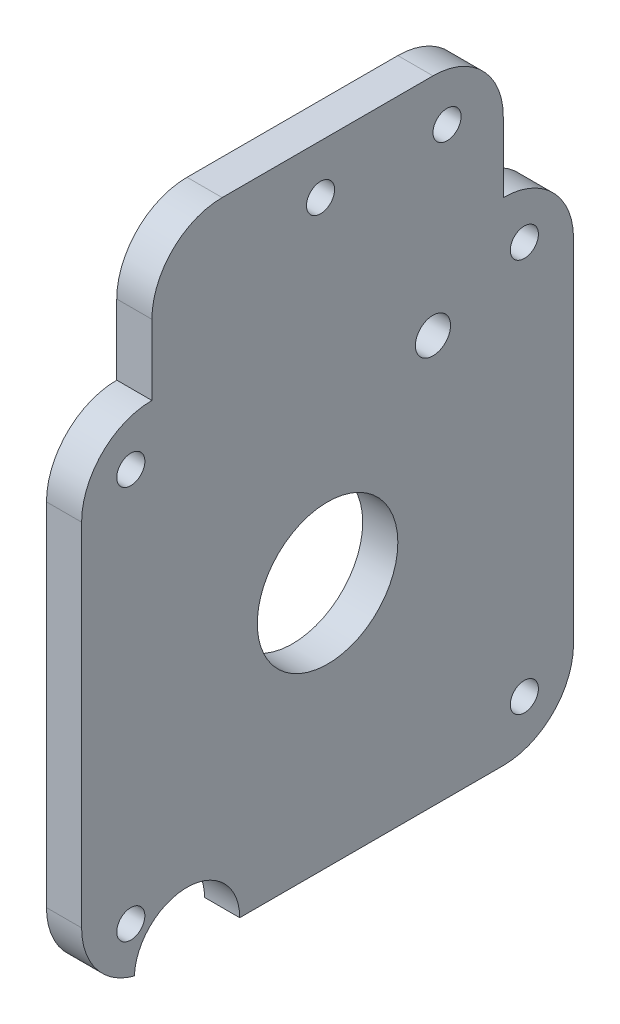
SolidWorks part; units mm, degrees
ref_plane "Alzado" through (0, 0, 0) normal (0, 0, 1) x (1, 0, 0)
ref_plane "Planta" through (0, 0, 0) normal (0, 1, 0) x (1, 0, 0)
ref_plane "Vista lateral" through (0, 0, 0) normal (1, 0, 0) x (0, 0, -1)
sketch "Croquis1" plane through (0, 0, 0) normal (1, 0, 0) x (0, 0, -1)
  line L0 (35, 70) -> (35, 35) construction
  line L1 (10, 0) -> (60, 0)
  line L2 (0, 10) -> (0, 60)
  line L3 (60, 70) -> (10, 70) construction
  line L4 (70, 10) -> (70, 60)
  line L5 (0, 35) -> (35, 35) construction
  line L8 (60, 70) -> (60, 80)
  line L9 (50, 90) -> (20, 90)
  line L10 (10, 70) -> (10, 80)
  arc A0 (10, 0) -> (0, 10) centre (10, 10) cw
  arc A1 (60, 0) -> (70, 10) centre (60, 10) ccw
  arc A2 (60, 70) -> (70, 60) centre (60, 60) cw
  arc A3 (0, 60) -> (10, 70) centre (10, 60) cw
  circle A4 centre (7, 63) radius 2
  circle A5 centre (63, 63) radius 2
  circle A6 centre (63, 7) radius 2
  circle A7 centre (7, 7) radius 2
  circle A8 centre (35, 35) radius 10
  arc A9 (20, 90) -> (10, 80) centre (20, 80) ccw
  arc A10 (60, 80) -> (50, 90) centre (50, 80) ccw
  point P7 (0, 0)
  point P12 (70, 70)
  point P15 (0, 70)
  point P34 (60, 90)
  dimension "D3" = 10
  dimension "D4" = 4
  dimension "D7" = 20
  dimension "D9" = 10
  dimension "D1" = 70
  dimension "D2" = 70
  dimension "D5" = 35
  dimension "D6" = 7
  dimension "D8" = 20
  dimension "D10" = 35
extrude "Saliente-Extruir1" add sketch "Croquis1" along normal blind 5
sketch "Croquis2" plane through (5, 0, 0) normal (1, 0, 0) x (0, 0, -1)
  line L0 (60, 70) -> (10, 70) construction
  line L1 (52, 83) -> (34, 83) construction
  line L2 (10, 0) -> (60, 0) construction
  line L3 (0, 60) -> (0, 10) construction
  line L4 (35, 35) -> (35, 70) construction
  line L5 (60, 70) -> (60, 80) construction
  circle A0 centre (15, 0) radius 7.5
  circle A1 centre (50, 58) radius 2.5
  arc A2 (10, 70) -> (0, 60) centre (10, 60) ccw construction
  circle A3 centre (52, 83) radius 2
  circle A4 centre (34, 83) radius 2
  dimension "D1" = 15
  dimension "D3" = 5
  dimension "D5" = 23
  dimension "D6" = 4
  dimension "D7" = 4
  dimension "D2" = 15
  dimension "D4" = 15
  dimension "D8" = 18
  dimension "D9" = 8
  dimension "D10" = 13
extrude "Cortar-Extruir1" cut sketch "Croquis2" against normal blind 10
sketch "Croquis3" plane through (0, 0, 0) normal (-1, 0, 0) x (0, 0, 1)
  line L6 (0, 10) -> (0, 60)
  line L7 (-10, 70) -> (-10, 80)
  line L8 (-20, 90) -> (-50, 90)
  line L9 (-60, 80) -> (-60, 70)
  line L10 (-70, 60) -> (-70, 10)
  line L11 (-60, 0) -> (-22.5, 0)
  line L12 (0, 10) -> (0, 60)
  line L13 (-10, 70) -> (-10, 80)
  line L14 (-20, 90) -> (-50, 90)
  line L15 (-60, 80) -> (-60, 70)
  line L16 (-70, 60) -> (-70, 10)
  line L17 (-60, 0) -> (-22.5, 0)
  circle A0 centre (-34, 83) radius 2 construction
  circle A1 centre (-7, 63) radius 2 construction
  circle A2 centre (-7, 7) radius 2 construction
  circle A3 centre (-35, 35) radius 10 construction
  circle A4 centre (-63, 7) radius 2 construction
  circle A5 centre (-50, 58) radius 2.5 construction
  circle A6 centre (-63, 63) radius 2 construction
  arc A7 (-7.5067, 0.3158) -> (-22.5, 0) centre (-15, 0) ccw
  arc A8 (-7.5067, 0.3158) -> (0, 10) centre (-10, 10) ccw
  arc A9 (0, 60) -> (-10, 70) centre (-10, 60) ccw
  arc A10 (-10, 80) -> (-20, 90) centre (-20, 80) ccw
  arc A11 (-50, 90) -> (-60, 80) centre (-50, 80) ccw
  arc A12 (-60, 70) -> (-70, 60) centre (-60, 60) ccw
  arc A13 (-70, 10) -> (-60, 0) centre (-60, 10) ccw
  arc A14 (-7.5067, 0.3158) -> (-22.5, 0) centre (-15, 0) ccw
  arc A15 (-7.5067, 0.3158) -> (0, 10) centre (-10, 10) ccw
  arc A16 (0, 60) -> (-10, 70) centre (-10, 60) ccw
  arc A17 (-10, 80) -> (-20, 90) centre (-20, 80) ccw
  arc A18 (-50, 90) -> (-60, 80) centre (-50, 80) ccw
  arc A19 (-60, 70) -> (-70, 60) centre (-60, 60) ccw
  arc A20 (-70, 10) -> (-60, 0) centre (-60, 10) ccw
  circle A21 centre (-52, 83) radius 2 construction
  circle A22 centre (-34, 83) radius 2
  circle A23 centre (-7, 63) radius 2
  circle A24 centre (-7, 7) radius 2
  circle A25 centre (-35, 35) radius 10
  circle A26 centre (-63, 7) radius 2
  circle A27 centre (-50, 58) radius 2.5
  circle A28 centre (-63, 63) radius 2
  circle A29 centre (-52, 83) radius 2
  dimension "D1" = 0
